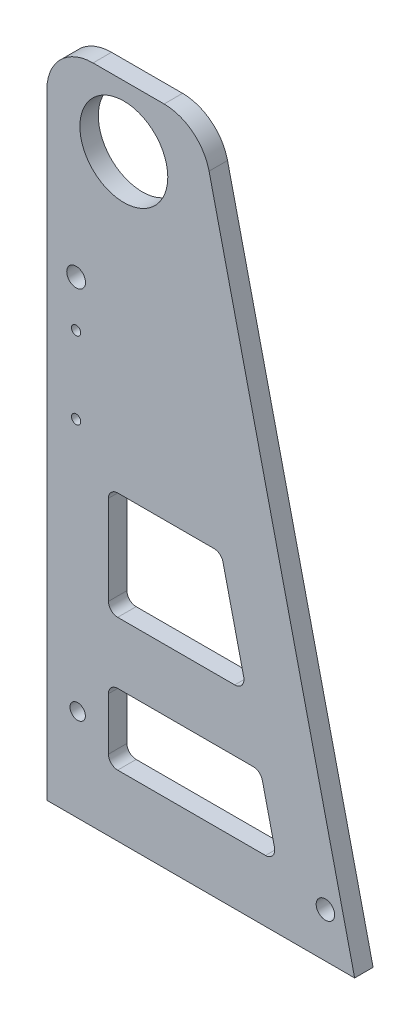
SolidWorks part; units mm, degrees
material "Policarbonato"
ref_plane "Plano frontal" through (0, 0, 0) normal (0, 0, 1) x (1, 0, 0)
ref_plane "Plano superior" through (0, 0, 0) normal (0, 1, 0) x (1, 0, 0)
ref_plane "Plano direito" through (0, 0, 0) normal (1, 0, 0) x (0, 0, -1)
sketch "Esboço1" plane through (0, 0, 0) normal (0, 0, 1) x (1, 0, 0)
  line L0 (0, 0) -> (0, 215)
  line L2 (100, 0) -> (0, 0)
  line L3 (0, 215) -> (50, 215)
  line L4 (50, 215) -> (100, 0)
  line L5 (10, 103) -> (10, 15) construction
  line L6 (25, 215) -> (25, 175) construction
  line L7 (10, 15) -> (75.7552, 15) construction
  line L8 (75.7552, 15) -> (55.2901, 103) construction
  line L9 (55.2901, 103) -> (10, 103) construction
  line L10 (20, 95) -> (20, 66)
  line L11 (23, 63) -> (61.0374, 63)
  line L12 (63.9594, 66.6795) -> (57.2152, 95.6795)
  line L13 (54.2932, 98) -> (23, 98)
  line L14 (20, 40) -> (20, 23)
  line L15 (23, 20) -> (71.0374, 20)
  line L16 (73.9594, 23.6795) -> (70.0059, 40.6795)
  line L17 (23, 43) -> (67.0839, 43)
  line L18 (0, 195) -> (50, 195) construction
  line L23 (17, 205) -> (33, 185) construction
  line L24 (17, 185) -> (33, 205) construction
  arc A8 (70.0059, 40.6795) -> (67.0839, 43) centre (67.0839, 40) ccw
  arc A9 (71.0374, 20) -> (73.9594, 23.6795) centre (71.0374, 23) ccw
  arc A10 (20, 23) -> (23, 20) centre (23, 23) ccw
  arc A11 (20, 40) -> (23, 43) centre (23, 40) cw
  arc A12 (57.2152, 95.6795) -> (54.2932, 98) centre (54.2932, 95) ccw
  arc A13 (61.0374, 63) -> (63.9594, 66.6795) centre (61.0374, 66) ccw
  arc A14 (20, 66) -> (23, 63) centre (23, 66) ccw
  arc A15 (20, 95) -> (23, 98) centre (23, 95) cw
  circle A20 centre (25, 195) radius 14.2875
  circle A21 centre (10, 30) radius 2.5
  point P8 (25, 195)
  point P49 (20, 63)
  dimension "D3" = 20
  dimension "D4" = 16
  dimension "D7" = 28.575
  dimension "D21" = 3
  dimension "D20" = 10
  dimension "D22" = 5
  dimension "D1" = 215
  dimension "D2" = 100
  dimension "D5" = 50
  dimension "D9" = 20
  dimension "D10" = 20
  dimension "D11" = 10
  dimension "D12" = 20
  dimension "D13" = 15
  dimension "D14" = 20
  dimension "D15" = 10
  dimension "D16" = 29
  dimension "D17" = 17
  dimension "D18" = 10
  dimension "D19" = 30
  dimension "D8" = 20
extrude "Ressalto-extrusão2" add sketch "Esboço1" along normal blind 6
fillet "Filete1" radius 15 2 edges at (0, 215, 3) (50, 215, 3)
sketch "Esboço3" plane through (0, 0, 0) normal (0, 0, -1) x (-1, 0, 0)
  line L1 (0, 0) -> (-100, 0) construction
  line L2 (0, 200) -> (0, 0) construction
  circle A0 centre (-9.5, 112) radius 1.5
  circle A1 centre (-90.5, 14.5) radius 3
  circle A2 centre (-9.5, 137) radius 1.5
  circle A3 centre (-9.5, 152) radius 3.05
  point P6 (-9.5, 112)
  point P9 (-9.5, 137)
  point P13 (0, 0)
  dimension "D5" = 6
  dimension "D1" = 25
  dimension "D6" = 3
  dimension "D7" = 112
  dimension "D8" = 15
  dimension "D9" = 6.1
  dimension "D2" = 9.5
  dimension "D3" = 14.5
  dimension "D4" = 9.5
extrude "Corte-extrusão1" cut sketch "Esboço3" against normal through all
